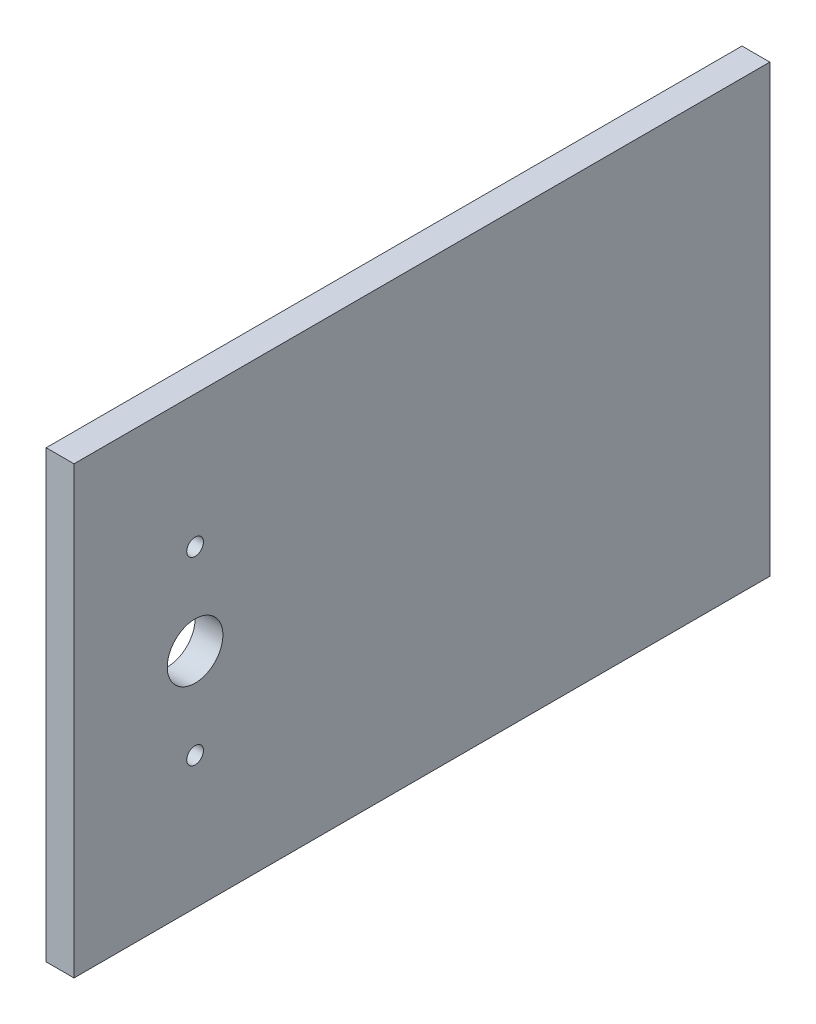
SolidWorks part; units mm, degrees
ref_plane "Front Plane" through (0, 0, 0) normal (1, 0, 0) x (0, 1, 0)
ref_plane "Top Plane" through (0, 0, 0) normal (0, 0, 1) x (0, 1, 0)
ref_plane "Right Plane" through (0, 0, 0) normal (0, 1, 0) x (-1, 0, 0)
sketch "Sketch1" plane through (0, 0, 0) normal (1, 0, 0) x (0, 1, 0)
  line L0 (-40, 40.75) -> (40, 40.75) construction
  line L1 (-40, -62.5) -> (40, -62.5)
  line L2 (-40, -62.5) -> (-40, 62.5)
  line L3 (-40, 62.5) -> (40, 62.5)
  line L4 (40, -62.5) -> (40, 62.5)
  line L5 (-40, -62.5) -> (40, 62.5) construction
  line L6 (-40, 62.5) -> (40, -62.5) construction
  line L7 (0, 62.5) -> (0, -62.5) construction
  circle A5 centre (0, 40.75) radius 5
  circle A6 centre (-16.22, 40.75) radius 1.5
  circle A7 centre (16.22, 40.75) radius 1.5
  point P0 (0, 0)
  dimension "D5" = 3
  dimension "D4" = 16.22
  dimension "D8" = 10
  dimension "D1" = 125
  dimension "D2" = 80
  dimension "D3" = 103.25
extrude "Boss-Extrude1" add sketch "Sketch1" along normal blind 5
